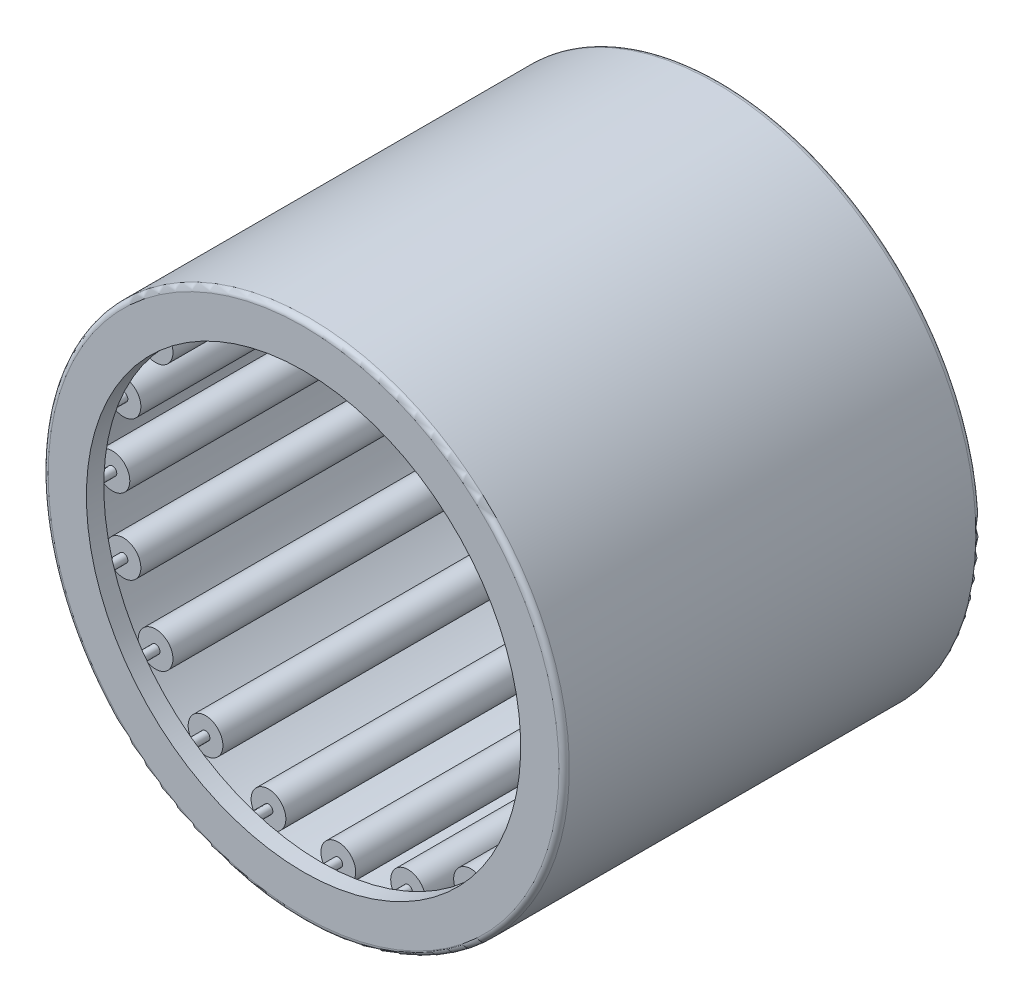
SolidWorks part; units mm, degrees
ref_plane "Front Plane" through (0, 0, 0) normal (0, 0, 1) x (1, 0, 0)
ref_plane "Top Plane" through (0, 0, 0) normal (0, 1, 0) x (1, 0, 0)
ref_plane "Right Plane" through (0, 0, 0) normal (1, 0, 0) x (0, 0, -1)
sketch "Sketch1" plane through (0, 0, 0) normal (1, 0, 0) x (0, 0, -1)
  line L0 (-12.7, 0) -> (12.7, 0) construction
  line L1 (0, 0) -> (0, 15.875) construction
  line L2 (-12.7, 0) -> (-12.7, 15.875) construction
  line L3 (-12.7, 15.875) -> (12.7, 15.875)
  line L4 (12.7, 15.875) -> (12.7, 0) construction
  line L5 (12.7, 0) -> (11.6417, 0) construction
  line L6 (11.6417, 0) -> (11.6417, 14.8167) construction
  line L7 (11.6417, 14.8167) -> (-11.6417, 14.8167)
  line L8 (-11.6417, 14.8167) -> (-11.6417, 0) construction
  line L9 (-11.6417, 0) -> (-12.7, 0) construction
  line L10 (-12.7, 15.875) -> (-12.7, 13.2292)
  line L11 (-12.7, 13.2292) -> (-11.6417, 13.2292)
  line L12 (-11.6417, 13.2292) -> (-11.6417, 14.8167)
  line L13 (11.6417, 15.875) -> (11.6417, 14.8167) construction
  line L14 (11.6417, 14.8167) -> (11.6417, 13.2292)
  line L15 (11.6417, 13.2292) -> (12.7, 13.2292)
  line L16 (12.7, 13.2292) -> (12.7, 15.875)
  line L17 (11.6417, 14.8167) -> (11.6417, 13.7583) construction
  line L18 (11.6417, 13.7583) -> (11.6417, 12.7) construction
  point P5 (0, 12.7)
  dimension "Width" = 25.4
  dimension "OD" = 31.75
  dimension "Shaft Dia" = 25.4
revolve "Revolve1" add sketch "Sketch1" angle 360 about L0
sketch "Sketch2" plane through (0, 0, 0) normal (1, 0, 0) x (0, 0, -1)
  line L0 (11.6417, 14.8167) -> (-11.6417, 14.8167) construction
  line L1 (-10.5833, 13.7583) -> (10.5833, 13.7583) construction
  line L2 (-10.5833, 13.7583) -> (-10.5833, 14.8167) construction
  line L3 (-10.5833, 14.8167) -> (10.5833, 14.8167)
  line L4 (10.5833, 13.7583) -> (10.5833, 14.8167) construction
  line L5 (11.6417, 13.2292) -> (12.7, 13.2292) construction
  line L6 (-11.6417, 13.7583) -> (-10.5833, 13.7583) construction
  line L7 (10.5833, 13.7583) -> (11.6417, 13.7583) construction
  line L8 (-12.7, 13.2292) -> (-11.6417, 13.2292) construction
  line L9 (-10.5833, 14.0229) -> (-10.5833, 13.4937) construction
  line L10 (-11.6417, 13.7583) -> (-11.6417, 13.2292) construction
  line L11 (-10.5833, 14.8167) -> (-10.5833, 14.0229)
  line L12 (10.5833, 14.8167) -> (10.5833, 14.0229)
  line L13 (10.5833, 14.0229) -> (-10.5833, 14.0229)
  line L14 (0, 14.8167) -> (0, 12.7) construction
  line L15 (-11.6417, 13.2292) -> (-11.6417, 14.8167) construction
  line L16 (-10.5833, 13.4937) -> (-11.6417, 13.4937) construction
  line L17 (0, 0) -> (12.7, 0) construction
  line L31 (12.7, -15.875) -> (12.7, 15.875) construction
  point P16 (0, 13.7583)
revolve "Revolve2" add sketch "Sketch2" angle 360 about L1
sketch "Sketch3" plane through (0, 0, 0) normal (1, 0, 0) x (0, 0, -1)
  line L0 (11.6417, 14.8167) -> (11.6417, 13.2292) construction
  line L1 (-11.6417, 13.7583) -> (11.6417, 13.7583)
  line L2 (-11.6417, 13.7583) -> (-11.6417, 14.0229)
  line L3 (-11.6417, 14.0229) -> (11.6417, 14.0229)
  line L4 (11.6417, 13.7583) -> (11.6417, 14.0229)
  line L5 (0, 0) -> (12.7, 0) construction
  line L6 (12.7, -15.875) -> (12.7, 15.875) construction
revolve "Revolve3" add sketch "Sketch3" angle 360 about L1
ref_axis "Axis1" through (0, 0, -12.7) along (0, 0, 1)
pattern_circular "CirPattern1" count 20 every 18 about axis through (0, 0, -12.7) along (0, 0, 1) of bodies 166 167
fillet "Fillet1" radius 0.3175 2 edges at (0, -15.875, -12.7) (0, -15.875, 12.7)
sketch "Sketch4" plane through (0, 0, 0) normal (1, 0, 0) x (0, 0, -1)
  line L1 (12.3825, 12.7) -> (10.5833, 12.7)
  line L2 (12.3825, 12.7) -> (12.3825, 13.2292)
  line L3 (12.3825, 13.2292) -> (10.5833, 13.2292)
  line L4 (10.5833, 12.7) -> (10.5833, 13.2292)
  line L5 (-12.7, 13.2292) -> (-11.6417, 13.2292) construction
  line L6 (12.3825, -15.875) -> (12.3825, 15.875) construction
  line L7 (10.5833, 14.8167) -> (10.5833, 14.0229) construction
revolve "Revolve4" [suppressed] add sketch "Sketch4" angle 360 about L0
sketch "Sketch5" plane through (0, 0, 0) normal (1, 0, 0) x (0, 0, -1)
  line L0 (-12.3825, 15.875) -> (-12.3825, -15.875) construction
  line L1 (-10.5833, 12.7) -> (-12.3825, 12.7)
  line L2 (-10.5833, 12.7) -> (-10.5833, 13.2292)
  line L3 (-10.5833, 13.2292) -> (-12.3825, 13.2292)
  line L4 (-12.3825, 12.7) -> (-12.3825, 13.2292)
  line L6 (-10.5833, 14.8167) -> (-10.5833, 14.0229) construction
  line L7 (-12.7, 13.2292) -> (-11.6417, 13.2292) construction
revolve "Revolve5" [suppressed] add sketch "Sketch5" angle 360 about L0
sketch "Front View" plane through (0, 0, 0) normal (0, 0, 1) x (1, 0, 0)
  circle A0 centre (0, 0) radius 12.7 construction
  circle A1 centre (0, 0) radius 15.875 construction
  dimension "OD" = 31.75
  dimension "ID" = 25.4
sketch "Right View" plane through (0, 0, 0) normal (1, 0, 0) x (0, 0, -1)
  line L0 (-12.7, 15.875) -> (12.7, 15.875) construction
  dimension "Width" = 25.4
ref_axis "Center Axis 1" through (0, 0, -12.3825) along (0, 0, 1)
ref_plane "Contact Plane 1" through (0, 0, 12.7) normal (0, 0, 1) x (1, 0, 0)
ref_plane "Contact Plane 2" through (0, 0, -12.7) normal (0, 0, -1) x (-1, 0, 0)
equation "\"Rollers@CirPattern1\" = \"OD@Sketch1\"*16"
equation "\"D1@Fillet1\" = \"OD@Sketch1\"*.01"
equation "\"Angle@CirPattern1\"= 360 / \"Rollers@CirPattern1\""
equation "\"OD@Front View\"=\"OD@Sketch1\""
equation "\"ID@Front View\"=\"Shaft Dia@Sketch1\""
equation "\"Width@Right View\"=\"Width@Sketch1\""
